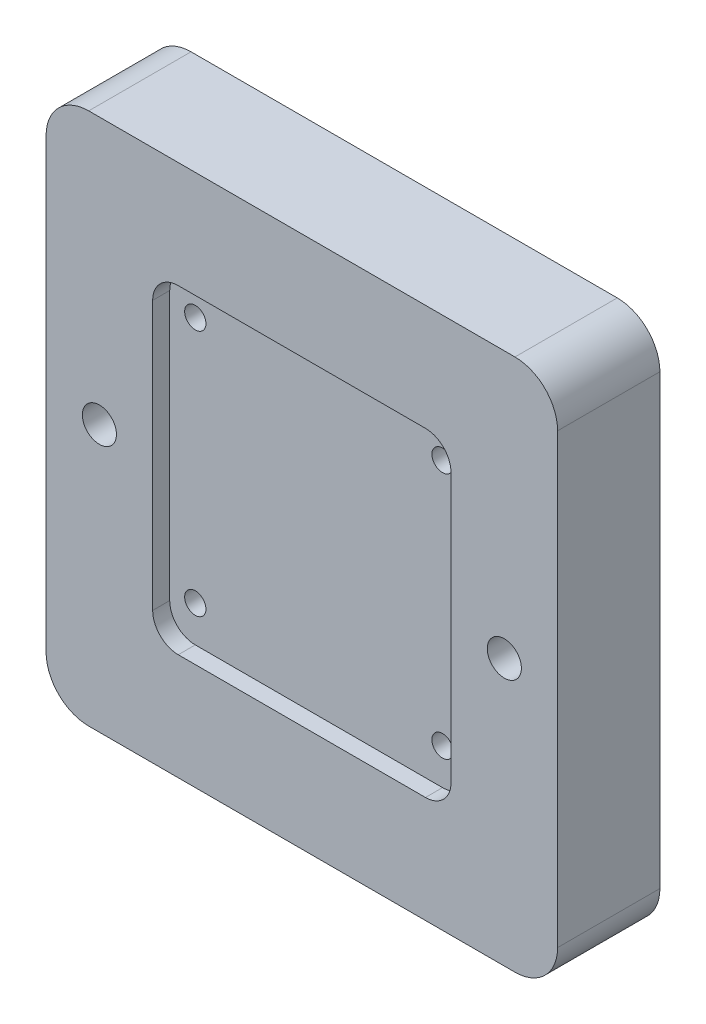
SolidWorks part; units mm, degrees
ref_plane "Front Plane" through (0, 0, 0) normal (0, 0, 1) x (1, 0, 0)
ref_plane "Top Plane" through (0, 0, 0) normal (0, 1, 0) x (1, 0, 0)
ref_plane "Right Plane" through (0, 0, 0) normal (1, 0, 0) x (0, 0, -1)
sketch "Sketch1" plane through (0, 0, 0) normal (0, 0, 1) x (1, 0, 0)
  line L0 (0, 62.5) -> (0, -62.5) construction
  line L1 (-50, 62.5) -> (50, 62.5)
  line L2 (-60, 52.5) -> (-60, -52.5)
  line L3 (-50, -62.5) -> (50, -62.5)
  line L4 (60, 52.5) -> (60, -52.5)
  line L5 (0, -62.5) -> (0, -37.5) construction
  line L6 (0, 37.5) -> (0, -37.5) construction
  line L7 (-29, 37.5) -> (29, 37.5)
  line L8 (-35, 31.5) -> (-35, -31.5)
  line L9 (-29, -37.5) -> (29, -37.5)
  line L10 (35, 31.5) -> (35, -31.5)
  line L11 (-35, 0) -> (-60, 0) construction
  line L12 (35, 0) -> (60, 0) construction
  arc A0 (50, 62.5) -> (60, 52.5) centre (50, 52.5) cw
  arc A1 (60, -52.5) -> (50, -62.5) centre (50, -52.5) cw
  arc A2 (-50, -62.5) -> (-60, -52.5) centre (-50, -52.5) cw
  arc A3 (-50, 62.5) -> (-60, 52.5) centre (-50, 52.5) ccw
  circle A4 centre (-47.5, 0) radius 4 construction
  circle A5 centre (47.5, 0) radius 4 construction
  arc A6 (-35, -31.5) -> (-29, -37.5) centre (-29, -31.5) ccw
  arc A7 (29, -37.5) -> (35, -31.5) centre (29, -31.5) ccw
  arc A8 (35, 31.5) -> (29, 37.5) centre (29, 31.5) ccw
  arc A9 (-29, 37.5) -> (-35, 31.5) centre (-29, 31.5) ccw
  point P31 (111.9206, -20.4692)
  point P32 (47.5, 0)
  point P39 (-47.5, 0)
  dimension "D1" = 10
  dimension "D2" = 8
  dimension "D3" = 6
  dimension "D4" = 70
  dimension "D5" = 75
  dimension "D6" = 25
extrude "Boss-Extrude1" add sketch "Sketch1" against normal blind 4
sketch "Sketch2" plane through (0, 0, -4) normal (0, 0, 1) x (1, 0, 0)
  line L8 (-50, -62.5) -> (50, -62.5) construction
  line L9 (60, 52.5) -> (60, -52.5) construction
  line L10 (-50, 62.5) -> (50, 62.5) construction
  line L11 (-60, 52.5) -> (-60, -52.5) construction
  line L12 (-50, -62.5) -> (50, -62.5)
  line L13 (60, 52.5) -> (60, -52.5)
  line L14 (-50, 62.5) -> (50, 62.5)
  line L15 (-60, 52.5) -> (-60, -52.5)
  arc A8 (50, -62.5) -> (60, -52.5) centre (50, -52.5) ccw construction
  arc A9 (60, 52.5) -> (50, 62.5) centre (50, 52.5) ccw construction
  arc A10 (-50, 62.5) -> (-60, 52.5) centre (-50, 52.5) ccw construction
  arc A11 (-60, -52.5) -> (-50, -62.5) centre (-50, -52.5) ccw construction
  arc A12 (50, -62.5) -> (60, -52.5) centre (50, -52.5) ccw
  arc A13 (60, 52.5) -> (50, 62.5) centre (50, 52.5) ccw
  arc A14 (-50, 62.5) -> (-60, 52.5) centre (-50, 52.5) ccw
  arc A15 (-60, -52.5) -> (-50, -62.5) centre (-50, -52.5) ccw
extrude "Boss-Extrude2" add sketch "Sketch2" against normal blind 20
sketch "Sketch3" plane through (0, 0, 0) normal (0, 0, 1) x (1, 0, 0)
  point P0 (-47.5, 0)
  point P3 (47.5, 0)
hole_wizard "Ø8.0mm Dowel Hole1" positions "Sketch3" profile "Sketch4" hole size "Ø8.0" standard "ANSI Metric"
sketch "Sketch4" plane through (-47.5, 0, 0) normal (1, 0, 0) x (0, -1, 0)
  line L0 (0, 0) -> (0, 20.4034)
  line L1 (0, 20.4034) -> (4, 18)
  line L2 (4, 18) -> (4, 0)
  line L5 (4, 0) -> (0, 0)
  line L10 (0, 20.4034) -> (-4, 18) construction
  line L11 (0, -6.35) -> (0, 107.95) construction
  dimension "Hole Dia." = 8
  dimension "Hole Depth" = 18
  dimension "Drill Angle" = 118
sketch "Sketch5" plane through (0, 0, -4) normal (0, 0, 1) x (1, 0, 0)
  line L0 (-29, 29) -> (29, -29) construction
  line L1 (-29, 29) -> (29, 29) construction
  line L2 (-29, 29) -> (-29, -29) construction
  line L3 (-29, -29) -> (29, -29) construction
  line L4 (29, 29) -> (29, -29) construction
  point P5 (-29, 29)
  point P7 (29, 29)
  point P8 (29, -29)
  point P9 (-29, -29)
  dimension "D1" = 58
sketch "Sketch6" plane through (0, 0, -4) normal (0, 0, 1) x (1, 0, 0)
  point P0 (-29, 29)
  point P3 (29, 29)
  point P6 (29, -29)
  point P9 (-29, -29)
hole_wizard "Tap Drill for M6x1.0 Tap1" positions "Sketch6" profile "Sketch7" hole size "M6x1.0" standard "ANSI Metric"
sketch "Sketch7" plane through (-29, 29, -4) normal (1, 0, 0) x (0, -1, 0)
  line L0 (0, 0) -> (0, 11.5022)
  line L1 (0, 11.5022) -> (2.5, 10)
  line L2 (2.5, 10) -> (2.5, 0)
  line L5 (2.5, 0) -> (0, 0)
  line L10 (0, 11.5022) -> (-2.5, 10) construction
  line L11 (0, -6.35) -> (0, 107.95) construction
  dimension "Hole Dia." = 5
  dimension "Hole Depth" = 10
  dimension "Drill Angle" = 118
sketch "Sketch8" [suppressed] plane through (0, 0, -24) normal (0, 0, -1) x (-1, 0, 0)
